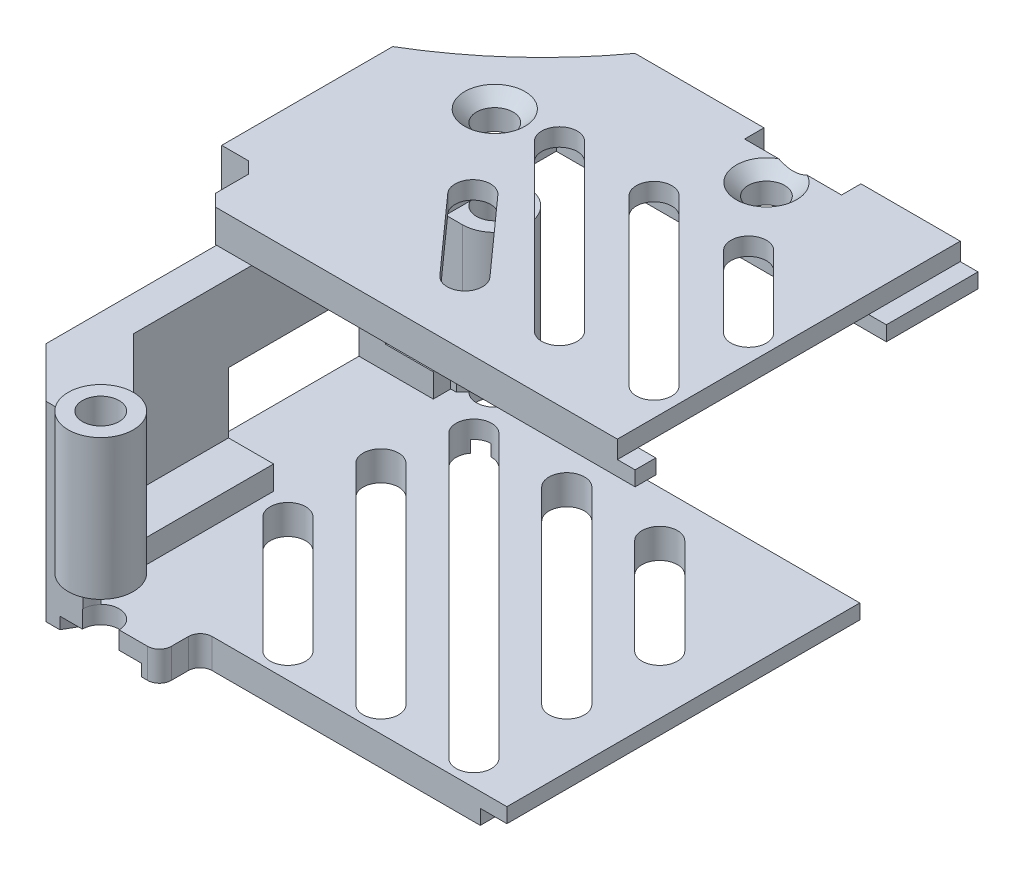
SolidWorks part; units mm, degrees
material "PPS"
ref_plane "前视基准面" through (0, 0, 0) normal (0, 0, 1) x (1, 0, 0)
ref_plane "上视基准面" through (0, 0, 0) normal (0, 1, 0) x (1, 0, 0)
ref_plane "右视基准面" through (0, 0, 0) normal (1, 0, 0) x (0, 0, -1)
sketch "基座草图-前" plane through (0, 0, 0) normal (0, 1, 0) x (1, 0, 0)
  line L2 (-24.7152, 2.0807) -> (-24.5, 0.3125)
  line L6 (-22.5, -14.2499) -> (-22.5, -7.2636)
  line L8 (-22.5, -7.2636) -> (-24.5, -7.2636)
  line L9 (-24.5, -7.2636) -> (-24.5, 0.3125)
  line L10 (-24.5, 0.3125) -> (-25.1116, 5.3379) construction
  line L12 (-26.5, 1.2398) -> (-26.5, -14.2499)
  line L13 (-26.5, -14.2499) -> (-22.5, -14.2499)
  line L16 (-4.1009, 11.812) -> (-4.1009, 8.358) construction
  line L17 (-4.1009, 8.358) -> (4.1009, 8.358)
  line L18 (4.1009, 8.358) -> (4.1009, 11.8106) construction
  line L19 (-16.253, 10) -> (-4.1009, 10)
  line L20 (-4.1009, 10) -> (-4.1009, 8.358)
  line L21 (4.1009, 8.358) -> (4.1009, 10)
  line L22 (0, 0.0001) -> (0, -23.6618) construction
  line L24 (4.1009, 10) -> (12.5, 10)
  line L25 (12.5, 10) -> (12.5, -14.2499)
  line L26 (12.5, -14.2499) -> (-26.5, -14.2499)
  arc A1 (-26.5, 2.4898) -> (-24.8662, 3.3216) centre (-28.6129, 8.6608) ccw construction
  arc A3 (-25.1116, 5.3379) -> (-57.77, 17.2644) centre (-45.4537, 0.3125) ccw construction
  arc A4 (-26.5, 1.2398) -> (-24.7152, 2.0807) centre (-28.3556, 7.493) ccw
  arc A5 (-17.503, 10) -> (-24.8662, 3.3216) centre (-44.5319, 32.4021) cw
  arc A6 (-16.253, 10) -> (-24.7152, 2.0807) centre (-44.1427, 31.321) cw
  circle A7 centre (0, 6.108) radius 1.55
  circle A8 centre (-16.866, 0) radius 1.55
  dimension "D1" = 1.25
  dimension "D2" = 1.25
  dimension "D3" = 1.25
  dimension "D4" = 16.866
  dimension "D5" = 12.5
  dimension "D6" = 9.9999
  dimension "D7" = 14.25
  dimension "D8" = 22.5
  dimension "D9" = 26.5
  dimension "D10" = 24.5
  dimension "D11" = 7.2637
extrude "基座-前" add sketch "基座草图-前" along normal blind 2.75 contours L19 A6 L2 L9 L8 L6 L26 L25 L24 L21 L17 L20 A8 A7 region at (-5.0831, 0, 2.6655)
sketch "基座草图-后" plane through (0, 0, 0) normal (0, 1, 0) x (1, 0, 0)
  line L0 (-22.5, -14.2499) -> (-22.5, -18.9999)
  line L1 (-22.5, -18.9999) -> (12.5, -18.9999)
  line L2 (12.5, -18.9999) -> (12.5, -14.2499)
  line L3 (12.5, 10) -> (12.5, -14.2499) construction
  line L4 (12.5, -14.2499) -> (-22.5, -14.2499) construction
  line L5 (-22.5, -14.2499) -> (12.5, -14.2499)
  dimension "D1" = 4.75
extrude "基座-后" add sketch "基座草图-后" along normal up to surface (2.75 mm away) up to face at (-16.866, 2.75, 1.55)
sketch "卡榫草图" plane through (0, 0, 0) normal (0, 1, 0) x (1, 0, 0)
  line L0 (-24.5, -7.2636) -> (-23.5, -7.2636)
  line L1 (-22.5, -7.2636) -> (-24.5, -7.2636) construction
  line L2 (-23.5, -7.2636) -> (-23.5, -14.2136)
  line L3 (-23.5, -14.2136) -> (-24.5, -14.2136)
  line L6 (-22.5, -18.9999) -> (-22.5, -7.2636) construction
  line L7 (-24.5, -14.2136) -> (-25.75, -14.2136)
  line L8 (-25.75, -14.2136) -> (-25.75, 0.3125)
  line L9 (-25.75, 0.3125) -> (-24.5, 0.3125) construction
  line L11 (-24.5, -7.2636) -> (-24.5, 0.3125) construction
  line L12 (-24.5, -7.2636) -> (-24.5, 0.3125)
  line L13 (-24.5, -7.2636) -> (-24.5, -14.2136)
  line L14 (-23.5, -7.2636) -> (-22.5, -7.2636)
  line L15 (-22.5, -7.2636) -> (-22.5, -14.2136)
  line L16 (-22.5, -14.2136) -> (-23.5, -14.2136)
  line L17 (-25.75, 0.3125) -> (-26.2135, 4.1214) construction
  line L18 (-24.7152, 2.0807) -> (-24.5, 0.3125) construction
  line L19 (-25.8753, 1.3423) -> (-25.75, 0.3125)
  line L20 (-24.7152, 2.0807) -> (-24.5, 0.3125)
  arc A0 (-24.7152, 2.0807) -> (-25.8753, 1.3423) centre (-44.1427, 31.321) cw
  arc A1 (-24.7152, 2.0807) -> (-16.253, 10) centre (-44.1427, 31.321) ccw construction
  dimension "D1" = 1
  dimension "D2" = 1.25
  dimension "D3" = 6.95
extrude "卡榫结构-1" add sketch "卡榫草图" along normal up to surface (2.75 mm away) contours L13 L12 L9 L8 L7 | L0 L13 L3 L2 | L12 L0 | L16 L15 L14 L2 region at (-25.1278, 0, 6.2521) region at (-24, 0, 10.7386) region at (-23, 0, 10.7386) up to face at (-16.866, 2.75, 1.55)
extrude "卡榫结构-2-注意PCB凸出部分" add sketch "草图5<4>" against normal blind 4 from surface contours L0 L13 L3 L2 | L13 L12 L9 L8 L7 region at (-25.1278, 0, 6.2521) region at (-24, 0, 10.7386) starting at face at (-9.4355, 0, 0.7086)
sketch "草图5<4>" plane through (0, 0, 0) normal (0, 1, 0) x (1, 0, 0) same geometry as "卡榫草图"
sketch "卡榫限位" plane through (0, 0, 0) normal (0, 1, 0) x (1, 0, 0)
  line L0 (12.5, 10) -> (14, 10)
  line L1 (14, 10) -> (14, -18.9999)
  line L2 (14, -18.9999) -> (12.5, -18.9999)
  line L3 (12.5, -18.9999) -> (12.5, 10)
  dimension "D1" = 1.5
extrude "限位结构" add sketch "卡榫限位" along normal blind 1.25
sketch "散热口位置" plane through (0, 0, 0) normal (0, 1, 0) x (1, 0, 0)
  line L0 (-13.916, -17.25) -> (-13.916, 2.25)
  line L1 (14, -18.9999) -> (14, 10) construction
  line L2 (-13.916, 2.25) -> (14, 2.25)
  line L4 (14, 2.25) -> (14, -17.25)
  line L5 (14, -17.25) -> (-13.916, -17.25)
  circle A0 centre (-16.866, 0) radius 1.55 construction
  dimension "D1" = 2.25
  dimension "D2" = 2.95
  dimension "D3" = 19.5
extrude "稳压PCB器件高度补偿" cut sketch "散热口位置" along normal blind 1.25
sketch "散热" plane through (0, 1.25, 0) normal (0, -1, 0) x (1, 0, 0)
  line L0 (0, 0) -> (24.2492, 0) construction
  line L1 (4.2339, -0.37) -> (10.2676, 5.6638) construction
  line L2 (3.1732, 0.6907) -> (9.2069, 6.7244)
  line L3 (5.2945, -1.4307) -> (11.3283, 4.6031)
  line L4 (-3.7661, -0.37) -> (10.1432, 13.5393) construction
  line L5 (-4.8268, 0.6907) -> (9.0825, 14.6)
  line L6 (-2.7055, -1.4307) -> (11.2038, 12.4787)
  line L7 (-11.7661, -0.37) -> (2.1432, 13.5393) construction
  line L8 (-12.8268, 0.6907) -> (1.0825, 14.6)
  line L9 (-10.7055, -1.4307) -> (3.2038, 12.4787)
  line L10 (4.2339, -0.37) -> (-3.7661, -0.37) construction
  line L11 (-3.7661, -0.37) -> (-11.7661, -0.37) construction
  line L12 (-5.8568, 13.5393) -> (-11.5554, 7.1695) construction
  line L13 (-4.7389, 12.5392) -> (-10.4375, 6.1694)
  line L14 (-6.9748, 14.5394) -> (-12.6734, 8.1696)
  line L15 (-5.8568, 13.5393) -> (2.1432, 13.5393) construction
  arc A0 (3.1732, 0.6907) -> (5.2945, -1.4307) centre (4.2339, -0.37) ccw
  arc A1 (11.3283, 4.6031) -> (9.2069, 6.7244) centre (10.2676, 5.6638) ccw
  arc A2 (-4.8268, 0.6907) -> (-2.7055, -1.4307) centre (-3.7661, -0.37) ccw
  arc A3 (11.2038, 12.4787) -> (9.0825, 14.6) centre (10.1432, 13.5393) ccw
  arc A4 (-12.8268, 0.6907) -> (-10.7055, -1.4307) centre (-11.7661, -0.37) ccw
  arc A5 (3.2038, 12.4787) -> (1.0825, 14.6) centre (2.1432, 13.5393) ccw
  arc A6 (-4.7389, 12.5392) -> (-6.9748, 14.5394) centre (-5.8568, 13.5393) ccw
  arc A7 (-12.6734, 8.1696) -> (-10.4375, 6.1694) centre (-11.5554, 7.1695) ccw
  point P5 (7.2507, 2.6469)
  point P14 (3.1885, 6.5847)
  point P20 (-4.8115, 6.5847)
  point P26 (-8.7061, 10.3544)
  dimension "D1" = 135
  dimension "D2" = 3
  dimension "D3" = 8
extrude "切除-拉伸2" cut sketch "散热" against normal through all
chamfer "倒角1" distance 1 angle 45 3 edges at (-20.6617, 2.75, -5.2238) (-22.5, 1.375, 18.9999) (-22.5, 1.375, 14.2136)
chamfer "倒角2" distance 1 angle 45 2 edges at (-16.866, 2.75, 1.55) (0, 2.75, -4.558)
sketch "草图1" plane through (0, -4, 0) normal (0, -1, 0) x (1, 0, 0)
  line L0 (-24.7152, -2.0807) -> (-24.5, -0.3125)
  line L1 (-24.5, -0.3125) -> (-24.5, 7.2636)
  line L2 (-24.5, 7.2636) -> (-23.5, 7.2636)
  line L3 (-23.5, 7.2636) -> (-23.5, 7.5136)
  line L4 (-23.5, 14.2136) -> (-23.5, 7.2636) construction
  line L5 (-23.5, 7.5136) -> (-24.75, 7.5136)
  line L8 (-24.9466, -1.9283) -> (-24.75, -0.3125)
  line L9 (-24.75, -0.3125) -> (-24.75, 7.5136)
  arc A0 (-24.7152, -2.0807) -> (-25.8753, -1.3423) centre (-44.1427, -31.321) ccw construction
  arc A1 (-24.9466, -1.9283) -> (-24.7152, -2.0807) centre (-44.1427, -31.321) cw
  point P18 (-24, 7.2636)
  dimension "D1" = 0.25
  dimension "D2" = 0.2482
  dimension "D3" = 0.25
extrude "公差切除" cut sketch "草图1" against normal up to surface (4 mm away) from surface up to face at (0, 0, -4.558) starting at face at (-24.7609, -4, 4.864)
sketch "侧面支撑" plane through (0, 0, 0) normal (0, 1, 0) x (1, 0, 0)
  line L0 (-23.5, -14.2136) -> (-25.75, -14.2136)
  line L1 (-25.75, -14.2136) -> (-25.75, 0.3125)
  line L2 (-25.75, 0.3125) -> (-25.8753, 1.3423)
  line L3 (-25.8753, 1.3423) -> (-24.9466, 1.9283)
  line L4 (-24.9466, 1.9283) -> (-24.75, 0.3125)
  line L5 (-24.75, 0.3125) -> (-24.75, -7.5136)
  line L6 (-24.75, -7.5136) -> (-23.5, -7.5136)
  line L7 (-23.5, -7.5136) -> (-23.5, -14.2136)
extrude "侧支撑_下" add sketch "侧面支撑" against normal blind 10.6 from surface starting at face at (-24.8525, -4, 4.9453)
sketch "螺柱草图" plane through (0, 0, 0) normal (0, 1, 0) x (1, 0, 0)
  line L0 (-16.866, 2.75) -> (-23.7437, 2.75)
  line L1 (-16.866, -2.75) -> (-24.75, -2.75) construction
  line L2 (-24.75, -7.5136) -> (-24.75, 0.3125) construction
  line L3 (-24.75, -2.75) -> (-24.75, 0.3125)
  line L4 (-24.75, 0.3125) -> (-24.9466, 1.9283)
  line L5 (-16.866, -2.75) -> (-20.808, -2.75)
  line L6 (-20.808, -2.75) -> (-24.75, -6.692) construction
  line L7 (-24.75, -6.692) -> (-24.75, -2.75) construction
  line L8 (-20.808, -2.75) -> (-22.779, -4.721)
  line L11 (-22.779, -4.721) -> (-22.779, -24.663)
  line L12 (-22.779, -24.663) -> (-16.9, -30.542)
  line L13 (-19.65, -33.292) -> (-21.531, -33.292)
  line L14 (-21.531, -33.292) -> (-25.75, -29.073)
  line L15 (-25.75, -29.073) -> (-25.75, -14.2136)
  line L16 (-25.75, -14.2136) -> (-24.75, -14.2136)
  line L18 (-24.75, -14.2136) -> (-24.75, -6.692)
  line L19 (-24.75, -6.692) -> (-24.75, -2.75)
  circle A0 centre (-16.866, 0) radius 1.55
  circle A1 centre (-16.866, 0) radius 1.55 construction
  circle A2 centre (-16.866, 0) radius 2.75 construction
  arc A3 (-24.9466, 1.9283) -> (-16.253, 10) centre (-44.1427, 31.321) ccw construction
  arc A4 (-16.866, 2.75) -> (-16.866, -2.75) centre (-16.866, 0) cw
  arc A5 (-23.7437, 2.75) -> (-24.9466, 1.9283) centre (-44.1427, 31.321) cw
  circle A6 centre (-16.9, -33.292) radius 1.55
  circle A7 centre (-16.9, -33.292) radius 2.75 construction
  arc A8 (-19.65, -33.292) -> (-16.9, -30.542) centre (-16.9, -33.292) ccw
  dimension "D1" = 5.5
  dimension "D2" = 45
  dimension "D3" = 135
  dimension "D4" = 135
extrude "模块底部支撑" add sketch "螺柱草图" along normal blind 10.25 from surface starting at face at (-24.8527, -14.6, 4.9449)
sketch "后螺柱" plane through (0, 0, 0) normal (0, 1, 0) x (1, 0, 0)
  circle A0 centre (-16.9, -33.292) radius 1.55
  circle A1 centre (-16.9, -33.292) radius 2.75
  circle A2 centre (-16.9, -33.292) radius 1.55 construction
  arc A3 (-19.65, -33.292) -> (-16.9, -30.542) centre (-16.9, -33.292) ccw construction
extrude "分电PCB板厚补偿" add sketch "后螺柱" along normal blind 1.6 from surface starting at face at (-16.866, -4.35, 1.55)
sketch "侧面外壳" plane through (0, 0, 0) normal (0, 1, 0) x (1, 0, 0)
  line L1 (-25.75, -29.073) -> (-25.75, 0.3125)
  line L3 (-25.8753, 1.3423) -> (-23.7437, 2.75)
  line L8 (-23.7437, 2.75) -> (-22.779, -4.721)
  line L9 (-22.779, -4.721) -> (-22.779, -24.663)
  line L10 (-22.779, -24.663) -> (-20.5905, -26.8515)
  line L11 (-16.9, -30.542) -> (-22.779, -24.663) construction
  line L12 (-20.5905, -26.8515) -> (-20.5905, -33.292)
  line L13 (-21.531, -33.292) -> (-19.65, -33.292) construction
  line L14 (-20.5905, -33.292) -> (-21.531, -33.292)
  line L15 (-21.531, -33.292) -> (-25.75, -29.073)
  line L18 (-25.8753, 1.3423) -> (-25.75, 0.3125)
  point P0 (0, 0)
extrude "1.0+0.4+2.0+2.5mm-侧面" add sketch "侧面外壳" against normal blind 5.9 from surface starting at face at (-21.3978, -14.6, 11.9481)
sketch "底盖" plane through (0, 0, 0) normal (0, 1, 0) x (1, 0, 0)
  line L0 (-23.7437, 2.75) -> (14, 2.75)
  line L1 (14, 2.25) -> (14, 10) construction
  line L2 (14, 2.75) -> (14, -33.292)
  line L3 (14, -33.292) -> (-20.5905, -33.292)
  line L4 (-20.5905, -33.292) -> (-20.5905, -26.8515)
  line L5 (-20.5905, -26.8515) -> (-22.779, -24.663)
  line L6 (-22.779, -24.663) -> (-22.779, -4.721)
  line L7 (-22.779, -4.721) -> (-23.7437, 2.75)
  line L8 (-18.416, 0) -> (-18.416, -32.969) construction
  line L9 (-16.866, 1.55) -> (14, 1.55) construction
  line L10 (14, 2.1) -> (-16.866, 2.1)
  line L11 (-18.966, 0) -> (-18.966, -33.292)
  line L12 (9.0539, -11.9717) -> (0.9895, -3.9073) construction
  line L13 (7.9932, -13.0323) -> (-0.0712, -4.9679)
  line L14 (10.1145, -10.911) -> (2.0501, -2.8466)
  line L15 (1.0825, -14.6) -> (-12.8268, -0.6907) construction
  line L16 (9.0539, -19.8325) -> (-6.8713, -3.9073) construction
  line L17 (7.9932, -20.8931) -> (-7.932, -4.9679)
  line L18 (10.1145, -18.7718) -> (-5.8107, -2.8466)
  line L19 (9.0539, -27.6933) -> (-14.7321, -3.9073) construction
  line L20 (7.9932, -28.7539) -> (-15.7928, -4.9679)
  line L21 (10.1145, -26.6326) -> (-13.6715, -2.8466)
  line L22 (9.0539, -11.9717) -> (9.0539, -19.8325) construction
  line L23 (9.0539, -19.8325) -> (9.0539, -27.6933) construction
  line L24 (1.1931, -27.6933) -> (-16.4822, -10.018) construction
  line L25 (0.1324, -28.7539) -> (-17.5429, -11.0786)
  line L26 (2.2537, -26.6326) -> (-15.4215, -8.9573)
  line L27 (-6.6677, -27.6933) -> (-16.4822, -17.8788) construction
  line L28 (-7.7284, -28.7539) -> (-17.5429, -18.9394)
  line L29 (-5.6071, -26.6326) -> (-15.4215, -16.8181)
  line L30 (9.0539, -27.6933) -> (1.1931, -27.6933) construction
  line L31 (1.1931, -27.6933) -> (-6.6677, -27.6933) construction
  circle A0 centre (-16.866, 0) radius 1.55 construction
  arc A1 (0.1324, -28.7539) -> (2.2537, -26.6326) centre (1.1931, -27.6933) ccw
  circle A2 centre (-16.9, -33.292) radius 1.55 construction
  arc A3 (-16.866, 2.1) -> (-18.966, 0) centre (-16.866, 0) ccw
  arc A4 (7.9932, -13.0323) -> (10.1145, -10.911) centre (9.0539, -11.9717) ccw
  arc A5 (2.0501, -2.8466) -> (-0.0712, -4.9679) centre (0.9895, -3.9073) ccw
  arc A6 (1.0825, -14.6) -> (3.2038, -12.4787) centre (2.1432, -13.5393) ccw construction
  arc A7 (7.9932, -20.8931) -> (10.1145, -18.7718) centre (9.0539, -19.8325) ccw
  arc A8 (-5.8107, -2.8466) -> (-7.932, -4.9679) centre (-6.8713, -3.9073) ccw
  arc A9 (7.9932, -28.7539) -> (10.1145, -26.6326) centre (9.0539, -27.6933) ccw
  arc A10 (-13.6715, -2.8466) -> (-15.7928, -4.9679) centre (-14.7321, -3.9073) ccw
  arc A11 (-15.4215, -8.9573) -> (-17.5429, -11.0786) centre (-16.4822, -10.018) ccw
  arc A12 (-7.7284, -28.7539) -> (-5.6071, -26.6326) centre (-6.6677, -27.6933) ccw
  arc A13 (-15.4215, -16.8181) -> (-17.5429, -18.9394) centre (-16.4822, -17.8788) ccw
  point P28 (5.0217, -7.9395)
  point P41 (1.0913, -11.8699)
  point P48 (-2.8391, -15.8003)
  point P58 (-11.575, -22.786)
  point P62 (-7.6446, -18.8556)
  dimension "D1" = 0.55
  dimension "D2" = 0.55
extrude "底盖主体" add sketch "底盖" along normal blind 4.5 from surface contours L10 A3 L11 L3 L2 A13 L29 A12 L28 A11 L26 A1 L25 A10 L21 A9 L20 A8 L18 A7 L17 A5 L14 A4 L13 | A3 L10 L2 L0 L7 L6 L5 L4 L3 L11 region at (-4.8718, 0, -2.2281) region at (13.5163, 0, 15.596) starting at face at (-23.2654, -20.5, 16.3875)
extrude "2.0mm-自组网元器件槽" cut sketch "底盖<3>" against normal blind 2 from surface contours L10 A3 L11 L3 L2 A13 L29 A12 L28 A11 L26 A1 L25 A10 L21 A9 L20 A8 L18 A7 L17 A5 L14 A4 L13 region at (13.5163, 0, 15.596) starting at face at (-11.7832, -16, 16.7599)
sketch "底盖<3>" plane through (0, 0, 0) normal (0, 1, 0) x (1, 0, 0) same geometry as "底盖"
sketch "螺母位" plane through (0, 0, 0) normal (0, 1, 0) x (1, 0, 0)
  line L1 (-15.1339, -3) -> (-13.4019, 0)
  line L2 (-13.4019, 0) -> (-15.1339, 3)
  line L3 (-15.1339, 3) -> (-18.598, 3)
  line L4 (-18.598, 3) -> (-20.3301, 0)
  line L5 (-20.3301, 0) -> (-18.598, -3)
  line L6 (-18.598, -3) -> (-15.1339, -3)
  line L7 (-15.1679, -36.292) -> (-13.4359, -33.292)
  line L8 (-13.4359, -33.292) -> (-15.1679, -30.292)
  line L9 (-15.1679, -30.292) -> (-18.6321, -30.292)
  line L10 (-18.6321, -30.292) -> (-20.3641, -33.292)
  line L11 (-20.3641, -33.292) -> (-18.6321, -36.292)
  line L12 (-18.6321, -36.292) -> (-15.1679, -36.292)
  circle A0 centre (-16.866, 0) radius 3 construction
  circle A1 centre (-16.9, -33.292) radius 3 construction
  circle A2 centre (-16.866, 0) radius 1.55
  circle A3 centre (-16.9, -33.292) radius 1.55
  dimension "D1" = 6
extrude "螺母" cut sketch "螺母位" along normal blind 1 from surface starting at face at (-13.5214, -20.5, 12.6432)
extrude "螺丝通孔" cut sketch "螺母位<3>" against normal through all and the other way through all contours A3 | A2 region at (-16.9, 0, 33.292)
sketch "螺母位<3>" plane through (0, 0, 0) normal (0, 1, 0) x (1, 0, 0) same geometry as "螺母位"
sketch "2+0.25mm-榫卯配合" plane through (0, 0, 0) normal (0, 1, 0) x (1, 0, 0)
  line L0 (14, 2.75) -> (11.75, 2.75)
  line L1 (11.75, 2.75) -> (11.75, -33.292)
  line L2 (-13.4359, -33.292) -> (14, -33.292) construction
  line L3 (11.75, -33.292) -> (14, -33.292)
  line L4 (14, -33.292) -> (14, 2.75)
  dimension "D1" = 2.25
extrude "1.25mm-榫卯结构" cut sketch "2+0.25mm-榫卯配合" along normal blind 1.25 from surface starting at face at (-13.1659, -20.5, 12.8522)
sketch "开关干涉切除草图" plane through (0, 0, 0) normal (0, 1, 0) x (1, 0, 0)
  line L0 (-11.366, 2.75) -> (-11.366, 0)
  line L1 (11.75, 2.75) -> (-14.9896, 2.75) construction
  line L2 (-11.366, 0) -> (14, 0)
  line L3 (14, 2.75) -> (14, -33.292) construction
  line L4 (14, 0) -> (14, 2.75)
  line L5 (14, 2.75) -> (-11.366, 2.75)
  line L6 (-16.866, 0) -> (16.6015, 0) construction
  line L7 (-16.9, -34.842) -> (0, -34.842) construction
  line L8 (-11.9359, -33.292) -> (-11.9359, -29.842)
  line L9 (-13.4359, -33.292) -> (11.75, -33.292) construction
  line L10 (-11.9359, -29.842) -> (14, -29.842)
  line L11 (14, -29.842) -> (14, -33.292)
  line L12 (14, -33.292) -> (-11.9359, -33.292)
  circle A0 centre (-16.9, -33.292) radius 1.55 construction
  dimension "D1" = 5.5
  dimension "D2" = 5
  dimension "D3" = 1.5
extrude "切除-拉伸8" cut sketch "开关干涉切除草图" along normal up to surface (-16 mm away) from surface up to face at (-13.7716, -16, 11.2684) starting at face at (-13.3705, -20.5, 12.8522)
sketch "PCB受力点" plane through (0, 0, 0) normal (0, 1, 0) x (1, 0, 0)
  line L0 (17.962, -1.096) -> (18.4923, -1.6263) construction
  line L1 (16.866, 2.3) -> (16.866, 1.55) construction
  line L2 (16.9, -33.292) -> (16.866, 0) construction
  line L3 (16.883, -16.646) -> (-20.855, -16.646) construction
  line L4 (16.866, -35.592) -> (16.866, -34.842) construction
  line L5 (17.962, -32.1959) -> (18.4923, -31.6656) construction
  line L6 (0, 0) -> (0, -42.5177) construction
  line L7 (-16.866, -35.592) -> (-16.866, -34.842)
  line L8 (-17.962, -32.1959) -> (-18.4923, -31.6656)
  line L9 (-16.866, 2.3) -> (-16.866, 1.55)
  line L10 (-17.962, -1.096) -> (-18.4923, -1.6263)
  line L11 (-18.4923, -31.6656) -> (-18.966, -31.6656)
  line L12 (-18.966, 0) -> (-18.966, -33.292) construction
  line L13 (-18.966, -31.6656) -> (-18.966, -32.3539)
  line L14 (-18.966, -1.6263) -> (-18.966, -0.9381)
  line L15 (-18.4923, -1.6263) -> (-18.966, -1.6263)
  line L16 (-19.166, -33.292) -> (-18.416, -33.292)
  line L17 (-21.531, -33.292) -> (-19.65, -33.292) construction
  circle A0 centre (16.866, 0) radius 1.55 construction
  circle A2 centre (16.866, 0) radius 2.3 construction
  arc A3 (17.962, -1.096) -> (16.866, 1.55) centre (16.866, 0) ccw construction
  arc A4 (16.866, 2.3) -> (18.4923, -1.6263) centre (16.866, 0) cw construction
  circle A5 centre (16.866, -33.292) radius 2.3 construction
  circle A6 centre (16.866, -33.292) radius 1.55 construction
  arc A7 (16.866, -35.592) -> (18.4923, -31.6656) centre (16.866, -33.292) ccw construction
  arc A8 (17.962, -32.1959) -> (16.866, -34.842) centre (16.866, -33.292) cw construction
  arc A9 (-17.962, -32.1959) -> (-16.866, -34.842) centre (-16.866, -33.292) ccw
  arc A10 (-16.866, -35.592) -> (-18.4923, -31.6656) centre (-16.866, -33.292) cw
  arc A11 (-17.962, -1.096) -> (-16.866, 1.55) centre (-16.866, 0) cw
  arc A12 (-16.866, 2.3) -> (-18.4923, -1.6263) centre (-16.866, 0) ccw
  dimension "D1" = 3.1
  dimension "D2" = 4.6
  dimension "D3" = 135
extrude "PCB受力" add sketch "PCB受力点" along normal up to surface (2 mm away) from surface contours A10 L16 A9 L8 | L13 A10 L11 | L9 A12 L10 A11 | A12 L14 L15 region at (-18.621, 0, 32.565) region at (-18.8181, 0, 31.8791) region at (-16.9115, 0, -1.925) region at (-18.8181, 0, 1.4129) up to face at (-18.8448, -16, 11.2684) starting at face at (-9.7851, -18, 16.9697)
sketch "RJ45插头" plane through (0, 0, 0) normal (0, 1, 0) x (1, 0, 0)
  line L0 (18.279, -16.6055) -> (22.279, -16.6055) construction
  line L1 (22.279, -16.6055) -> (22.279, -3.1055) construction
  line L2 (22.279, -3.1055) -> (18.279, -3.1055) construction
  line L3 (18.279, -3.1055) -> (18.279, -16.6055) construction
  line L7 (0, 0) -> (0, -40.5206) construction
  line L8 (-18.279, -3.1055) -> (-18.279, -16.6055)
  line L9 (-22.279, -3.1055) -> (-18.279, -3.1055)
  line L10 (-22.279, -16.6055) -> (-22.279, -3.1055)
  line L11 (-18.279, -16.6055) -> (-22.279, -16.6055)
  dimension "D3" = 4
extrude "插头干涉切除-1" cut sketch "RJ45插头" along normal up to surface (18 mm away) from surface up to face at (-9.2467, 0, 3.7825) starting at face at (-11.7463, -18, 14.6884)
sketch "RJ45插头-2" plane through (0, 0, 0) normal (1, 0, 0) x (0, 0, -1)
  line L0 (-16.6055, -10.85) -> (-3.1055, -10.85)
  line L1 (-3.1055, -10.85) -> (-3.1055, -18)
  line L2 (-3.1055, -18) -> (-16.6055, -18)
  line L3 (-16.6055, -18) -> (-16.6055, -10.85)
  line L10 (-16.6055, -16) -> (-16.6055, -18) construction
  line L11 (-3.1055, -18) -> (-3.1055, -16) construction
  line L13 (-3.1055, -18) -> (-16.6055, -18) construction
  line L14 (-16.6055, -16) -> (-31.6656, -16) construction
  dimension "D1" = 5.15
extrude "切除-拉伸11" cut sketch "RJ45插头-2" against normal through all and the other way through all
chamfer "倒角3" distance 0.5 angle 45 4 edges at (-25.75, -18, 9.8555) (-25.75, -14.425, 16.6055) (-25.75, -10.85, 9.8555) (-25.75, -14.425, 3.1055)
fillet "圆角1" radius 1 6 edges at (-11.9359, -19.25, 33.292) (-11.9359, -19.25, 29.842) (-11.366, -18.25, -2.75) (-11.366, -19.25, 0) (-19.65, -9.475, 33.292) (-16.9, -9.475, 30.542)
